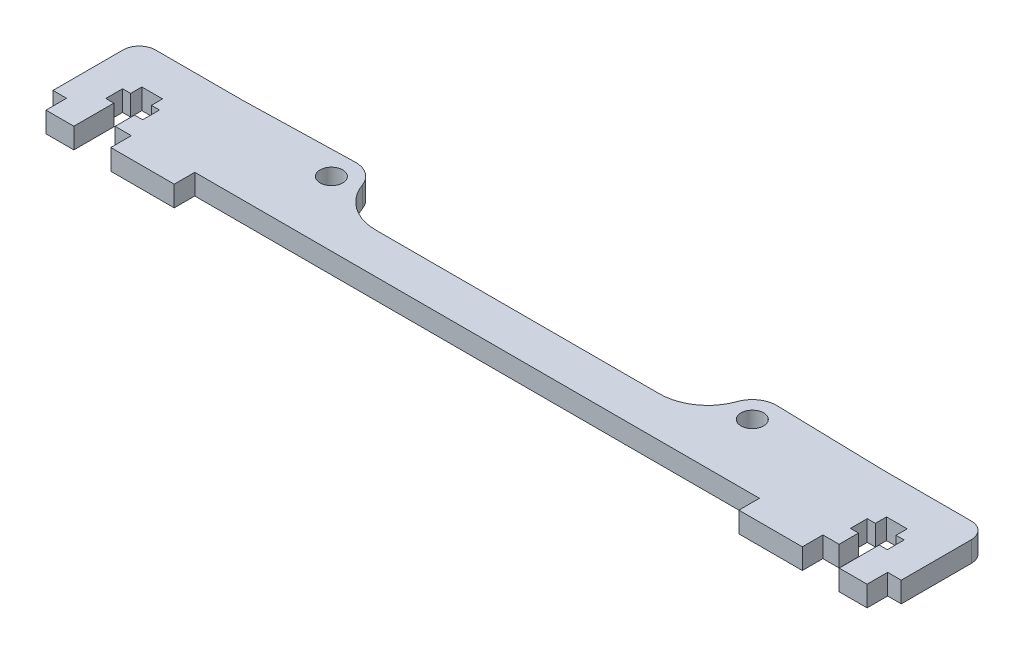
SolidWorks part; units mm, degrees
ref_plane "Front Plane" through (0, 0, 0) normal (0, 0, 1) x (1, 0, 0)
ref_plane "Top Plane" through (0, 0, 0) normal (0, 1, 0) x (1, 0, 0)
ref_plane "Right Plane" through (0, 0, 0) normal (1, 0, 0) x (0, 0, -1)
sketch "Sketch1" plane through (0, 0, 0) normal (0, 1, 0) x (1, 0, 0)
  line L0 (28.75, 0) -> (28.75, -3.75)
  line L1 (28.75, -3.75) -> (-28.75, -3.75)
  line L2 (36.25, 0) -> (36.25, -3.75)
  line L3 (36.25, -3.75) -> (49.5, -3.75)
  line L4 (65.5, 3.325) -> (65.5, -10)
  line L5 (65.5, -10) -> (-65.5, -10)
  line L6 (0, -10) -> (0, -3.75) construction
  line L7 (55.9, -10) -> (55.9, -7)
  line L8 (55.9, -7) -> (54.65, -7)
  line L9 (54.65, -7) -> (54.65, -4.4)
  line L10 (54.65, -4.4) -> (55.9, -4.4)
  line L11 (55.9, -4.4) -> (55.9, -2.675)
  line L12 (55.9, -2.675) -> (59.1, -2.675)
  line L13 (59.1, -2.675) -> (59.1, -4.4)
  line L14 (59.1, -4.4) -> (60.35, -4.4)
  line L15 (60.35, -4.4) -> (60.35, -7)
  line L16 (60.35, -7) -> (59.1, -7)
  line L17 (59.1, -7) -> (59.1, -10)
  line L18 (57.5, -2.675) -> (57.5, -10) construction
  line L19 (49.5, -3.75) -> (49.5, 3.325)
  line L20 (49.5, 3.325) -> (65.5, 3.325)
  line L21 (57.5, -2.675) -> (65.5, -2.675) construction
  line L22 (57.5, -2.675) -> (49.5, -2.675) construction
  line L23 (-57.5, -2.675) -> (-49.5, -2.675) construction
  line L24 (53.4, -10) -> (43.6, -10)
  line L25 (53.4, -10) -> (53.4, -13.175)
  line L26 (53.4, -13.175) -> (43.6, -13.175)
  line L27 (43.6, -10) -> (43.6, -13.175)
  line L28 (-57.5, -2.675) -> (-65.5, -2.675) construction
  line L29 (-57.5, -2.675) -> (-57.5, -10) construction
  line L30 (-43.6, -10) -> (-43.6, -13.175)
  line L31 (-53.4, -13.175) -> (-43.6, -13.175)
  line L32 (-53.4, -10) -> (-53.4, -13.175)
  line L33 (-53.4, -10) -> (-43.6, -10)
  line L34 (-49.5, 3.325) -> (-65.5, 3.325)
  line L35 (-49.5, -3.75) -> (-49.5, 3.325)
  line L36 (-59.1, -7) -> (-59.1, -10)
  line L37 (-60.35, -7) -> (-59.1, -7)
  line L38 (-60.35, -4.4) -> (-60.35, -7)
  line L39 (-59.1, -4.4) -> (-60.35, -4.4)
  line L40 (-59.1, -2.675) -> (-59.1, -4.4)
  line L41 (-55.9, -2.675) -> (-59.1, -2.675)
  line L42 (-55.9, -4.4) -> (-55.9, -2.675)
  line L43 (-54.65, -4.4) -> (-55.9, -4.4)
  line L44 (-54.65, -7) -> (-54.65, -4.4)
  line L45 (-55.9, -7) -> (-54.65, -7)
  line L46 (-55.9, -10) -> (-55.9, -7)
  line L47 (-65.5, 3.325) -> (-65.5, -10)
  line L48 (-36.25, -3.75) -> (-49.5, -3.75)
  line L49 (-36.25, 0) -> (-36.25, -3.75)
  line L50 (-28.75, 0) -> (-28.75, -3.75)
  line L51 (59.1, -10) -> (59.1, -13.175)
  line L52 (-59.1, -10) -> (-63.4, -10)
  line L53 (-59.1, -10) -> (-59.1, -13.175)
  line L54 (-59.1, -13.175) -> (-63.4, -13.175)
  line L55 (-63.4, -10) -> (-63.4, -13.175)
  line L56 (63.4, -10) -> (63.4, -13.175)
  line L57 (59.1, -13.175) -> (63.4, -13.175)
  line L58 (32.5, 3.75) -> (49.5, 3.325)
  line L59 (-32.5, 3.75) -> (-49.5, 3.325)
  circle A0 centre (32.5, 0) radius 1.75
  circle A1 centre (32.5, 0) radius 3.75
  circle A2 centre (-32.5, 0) radius 3.75
  circle A3 centre (-32.5, 0) radius 1.75
  dimension "D1" = 32.5
  dimension "D2" = 3.5
  dimension "D3" = 2
  dimension "D4" = 10
  dimension "D5" = 65.5
  dimension "D6" = 1.6
  dimension "D7" = 57.5
  dimension "D8" = 2.85
  dimension "D9" = 2.85
  dimension "D10" = 2.6
  dimension "D11" = 3
  dimension "D12" = 7.325
  dimension "D13" = 6
  dimension "D14" = 4.1
  dimension "D15" = 9.8
  dimension "D16" = 3.175
  dimension "D17" = 4.3
  dimension "D18" = 3.175
extrude "Boss-Extrude1" add sketch "Sketch1" along normal blind 3.175 contours L50 A2 L49 L48 L35 L34 L47 L5 L36 L37 L38 L39 L40 L41 L42 L43 L44 L45 L46 L7 L8 L9 L10 L11 L12 L13 L14 L15 L16 L17 L4 L20 L19 L3 L2 A1 L0 L1 | L5 L32 L31 L30 | A2 A3 | A1 A0 | L5 L27 L26 L25 | L5 L55 L54 L53 | L51 L57 L56 L5 | L49 A2 L59 L35 L48 | A1 L2 L3 L19 L58 region at (0, 0, 5.3552) region at (29.9233, 0, -2.5767) region at (42.6119, 0, 0.043) region at (-32.5, 0, 3.6439) region at (-42.6119, 0, 0.043) region at (61.25, 0, 11.5875) region at (-61.25, 0, 11.5875) region at (48.5, 0, 11.5875) region at (-48.5, 0, 11.5875)
fillet "Fillet1" radius 7.5 2 edges at (-28.75, 1.5875, 3.75) (28.75, 1.5875, 3.75)
fillet "Fillet2" radius 2.5 2 edges at (-65.5, 1.5875, -3.325) (65.5, 1.5875, -3.325)
